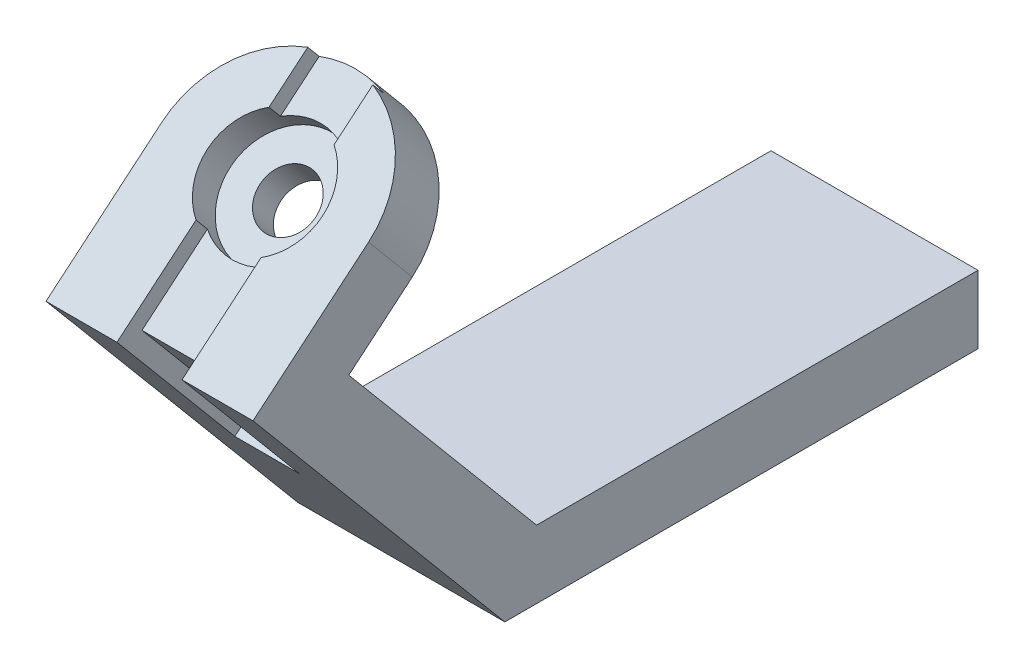
SolidWorks part; units mm, degrees
ref_plane "Front Plane" through (0, 0, 0) normal (0, 0, 1) x (1, 0, 0)
ref_plane "Top Plane" through (0, 0, 0) normal (0, 1, 0) x (1, 0, 0)
ref_plane "Right Plane" through (0, 0, 0) normal (1, 0, 0) x (0, 0, -1)
sketch "Sketch1" plane through (0, 0, 0) normal (1, 0, 0) x (0, 0, -1)
  line L0 (0, 0) -> (-149.2749, 0)
  line L1 (-149.2749, 0) -> (-212.7648, 75.6643)
  line L2 (-212.7648, 75.6643) -> (-191.3155, 93.6623)
  line L3 (-191.3155, 93.6623) -> (-206.0997, 111.2814)
  line L4 (-206.0997, 111.2814) -> (-245.1679, 78.4992)
  line L5 (-245.1679, 78.4992) -> (-160, -23)
  line L6 (-160, -23) -> (0, -23)
  line L7 (0, -23) -> (0, 0)
  line L8 (-160, -23) -> (-243.956, -23) construction
  dimension "D1" = 23
  dimension "D2" = 23
  dimension "D3" = 23
  dimension "D4" = 160
  dimension "D5" = 50
  dimension "D6" = 51
extrude "Boss-Extrude1" add sketch "Sketch1" against normal blind 70
sketch "Sketch3" plane through (0, 166.7868, 139.9508) normal (0, 0.766, 0.6428) x (1, 0, 0)
  line L0 (-70, -86.3512) -> (0, -86.3512) construction
  arc A0 (-70, -86.3512) -> (0, -86.3512) centre (-35, -86.3512) cw
  circle A1 centre (-35, -86.3512) radius 19.5
  circle A2 centre (-35, -86.3512) radius 9.5
  line M2 (0, -86.3512) -> (-70, -86.3512)
  dimension "D1" = 39
  dimension "D2" = 19
extrude "Boss-Extrude2" add sketch "Sketch3" against normal blind 23 contours A1 A0 M2 | A2 A1 M2 | A2 A1 M2 | A1 region at (-35, 133.2759, 179.8876) region at (-35, 105.1126, 213.4513) region at (-35, 117.4501, 198.748)
extrude "Cut-Extrude1" cut sketch "Sketch3<3>" against normal blind 23 contours A2 M2 | A2 M2 region at (-35, 108.6897, 209.1883) region at (-35, 113.873, 203.011)
sketch "Sketch3<3>" plane through (0, 166.7868, 139.9508) normal (0, 0.766, 0.6428) x (1, 0, 0) same geometry as "Sketch3"
extrude "Cut-Extrude2" cut sketch "Sketch3<4>" against normal blind 12 contours A2 A1 M2 | A2 A1 M2 region at (-35, 105.1126, 213.4513) region at (-35, 117.4501, 198.748)
sketch "Sketch3<4>" plane through (0, 166.7868, 139.9508) normal (0, 0.766, 0.6428) x (1, 0, 0) same geometry as "Sketch3"
sketch "Sketch4" plane through (0, 166.7868, 139.9508) normal (0, 0.766, 0.6428) x (1, 0, 0)
  line L0 (-35, -51.3512) -> (-35, -142.9254) construction
  line L1 (-70, -137.3512) -> (0, -137.3512) construction
  line L2 (-46, -137.3512) -> (-24, -137.3512)
  line L3 (-46, -137.3512) -> (-46, -44.7492)
  line L4 (-46, -44.7492) -> (-24, -44.7492)
  line L5 (-24, -137.3512) -> (-24, -44.7492)
  arc A0 (0, -86.3512) -> (-70, -86.3512) centre (-35, -86.3512) ccw construction
  dimension "D1" = 22
extrude "Cut-Extrude3" cut sketch "Sketch4" against normal blind 6
sketch "Sketch5" plane through (0, -88.2877, 105.2171) normal (0, -0.6428, 0.766) x (1, 0, 0)
  line L1 (-46, 211.7248) -> (-24, 211.7248)
  line L2 (-46, 211.7248) -> (-46, 155.7248)
  line L3 (-46, 155.7248) -> (-24, 155.7248)
  line L4 (-24, 211.7248) -> (-24, 155.7248)
  dimension "D1" = 22
  dimension "D2" = 56
extrude "Cut-Extrude4" cut sketch "Sketch5" against normal blind 6
